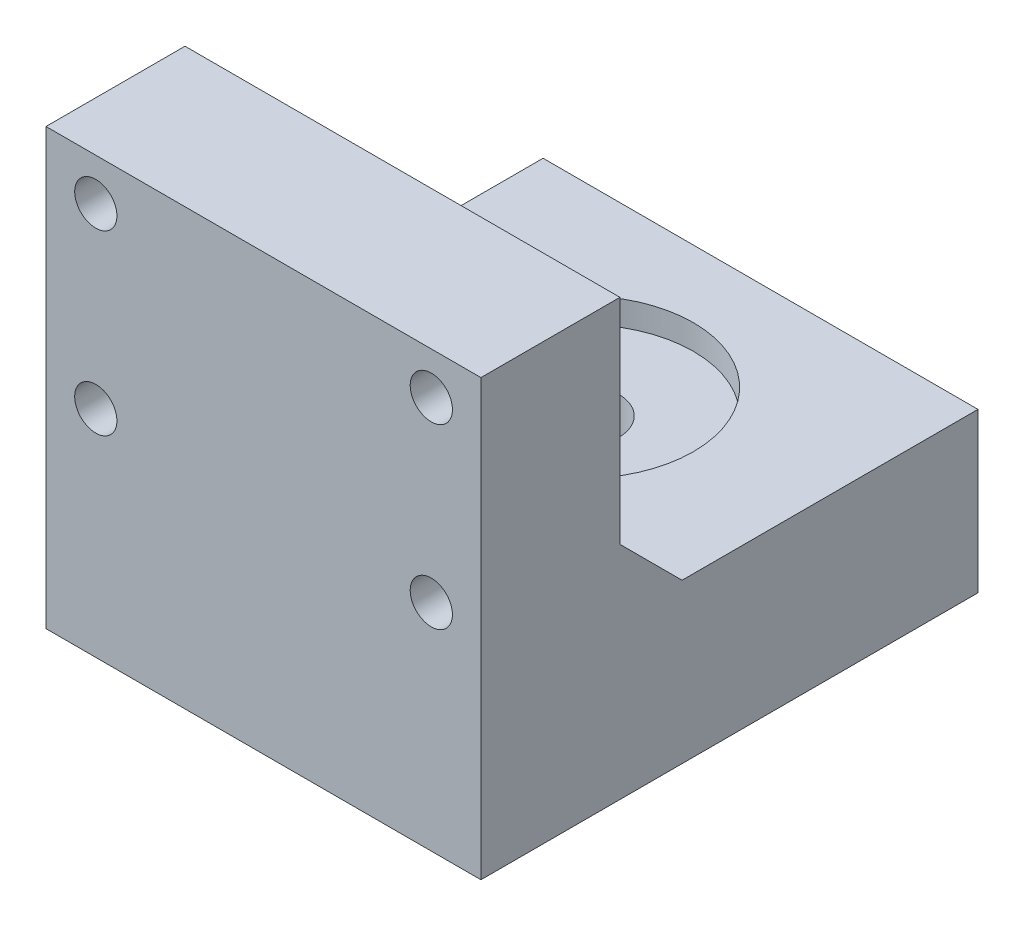
SolidWorks part; units mm, degrees
ref_plane "Front Plane" through (0, 0, 0) normal (0, 0, 1) x (1, 0, 0)
ref_plane "Top Plane" through (0, 0, 0) normal (0, 1, 0) x (1, 0, 0)
ref_plane "Right Plane" through (0, 0, 0) normal (1, 0, 0) x (0, 0, -1)
sketch "Sketch1" plane through (0, 0, 0) normal (1, 0, 0) x (0, 0, -1)
  line L0 (0, 35) -> (0, 0)
  line L1 (0, 0) -> (40, 0)
  line L2 (11.1869, 12.785) -> (40, 12.785)
  line L3 (11.1869, 35) -> (11.1869, 12.785)
  line L4 (0, 35) -> (11.1869, 35)
  line L5 (40, 12.785) -> (40, 0)
  line L6 (11.1869, 35) -> (11.1869, 0) construction
  line L7 (0, 12.785) -> (40, 12.785) construction
  dimension "D1" = 35
  dimension "D2" = 40
  dimension "D4" = 11.1869
  dimension "D3" = 12.785
extrude "Boss-Extrude1" add sketch "Sketch1" along normal blind 35
sketch "Sketch3" plane through (0, 12.785, 0) normal (0, 1, 0) x (1, 0, 0)
  circle A0 centre (17.5, 25.5934) radius 9
  circle A1 centre (17.5, 25.5934) radius 3.0015
  dimension "D1" = 18
  dimension "D2" = 6.003
extrude "Cut-Extrude1" cut sketch "Sketch3" against normal through all contours A1
extrude "Cut-Extrude2" cut sketch "Sketch3<5>" against normal blind 2 contours A0
sketch "Sketch3<5>" plane through (0, 12.785, 0) normal (0, 1, 0) x (1, 0, 0) same geometry as "Sketch3"
sketch "Sketch4" plane through (0, 0, -11.1869) normal (0, 0, -1) x (-1, 0, 0)
  circle A0 centre (-31.0068, 31.6165) radius 1.7
  circle A1 centre (-31.0068, 17.3328) radius 1.7
  circle A2 centre (-4.0068, 17.3328) radius 1.7
  circle A3 centre (-4.0068, 31.6165) radius 1.7
  dimension "D1" = 3.4
  dimension "D2" = 2
  dimension "D3" = 2
extrude "Cut-Extrude3" cut sketch "Sketch4" against normal through all
chamfer "Chamfer1" distance 5 angle 45 1 edges at (17.5, 12.785, -11.1869)
equation "\"P\"= 300"
equation "\"E\"= 3500"
equation "\"w\"= 35"
equation "\"L1\"=40"
equation "\"L2\"= 35"
equation "\"def\"= 0.30"
equation "\"t1\"= ( 4 * \"P\" * \"L1\" ^ 3 / ( \"E\" * \"w\" * \"def\" ) ) ^ ( 1 / 3 )"
equation "\"t2\"= ( 4 * \"P\" * \"L2\" ^ 3 / ( \"E\" * \"w\" * \"def\" ) ) ^ ( 1 / 3 )"
equation "\"D1@Sketch1\"=\"L2\""
equation "\"D2@Sketch1\"=\"L1\""
equation "\"D4@Sketch1\"=\"t2\""
equation "\"D3@Sketch1\"=\"t1\""
equation "\"D1@Boss-Extrude1\"=\"L2\""
